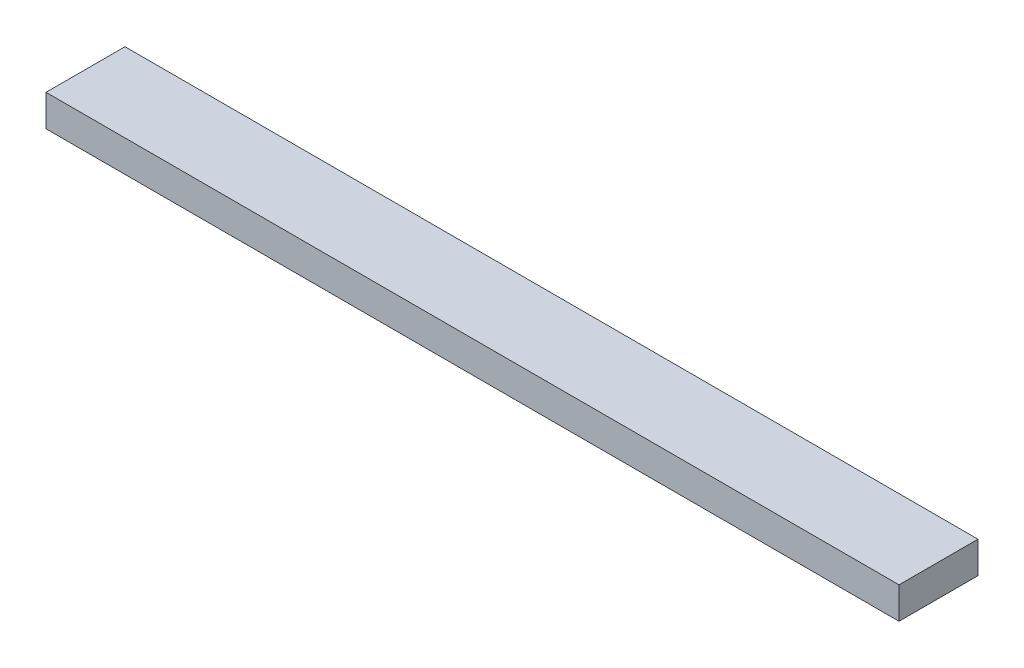
SolidWorks part; units mm, degrees
ref_plane "Спереди" through (0, 0, 0) normal (0, 0, 1) x (1, 0, 0)
ref_plane "Сверху" through (0, 0, 0) normal (0, 1, 0) x (1, 0, 0)
ref_plane "Справа" through (0, 0, 0) normal (1, 0, 0) x (0, 0, -1)
sketch "Эскиз1" plane through (0, 0, 0) normal (0, 1, 0) x (1, 0, 0)
  line L1 (-270, 25) -> (270, 25)
  line L2 (-270, 25) -> (-270, -25)
  line L3 (-270, -25) -> (270, -25)
  line L4 (270, 25) -> (270, -25)
  line L5 (-270, 25) -> (270, -25) construction
  line L6 (-270, -25) -> (270, 25) construction
  point P0 (0, 0)
extrude "Бобышка-Вытянуть1" add sketch "Эскиз1" along normal blind 20
